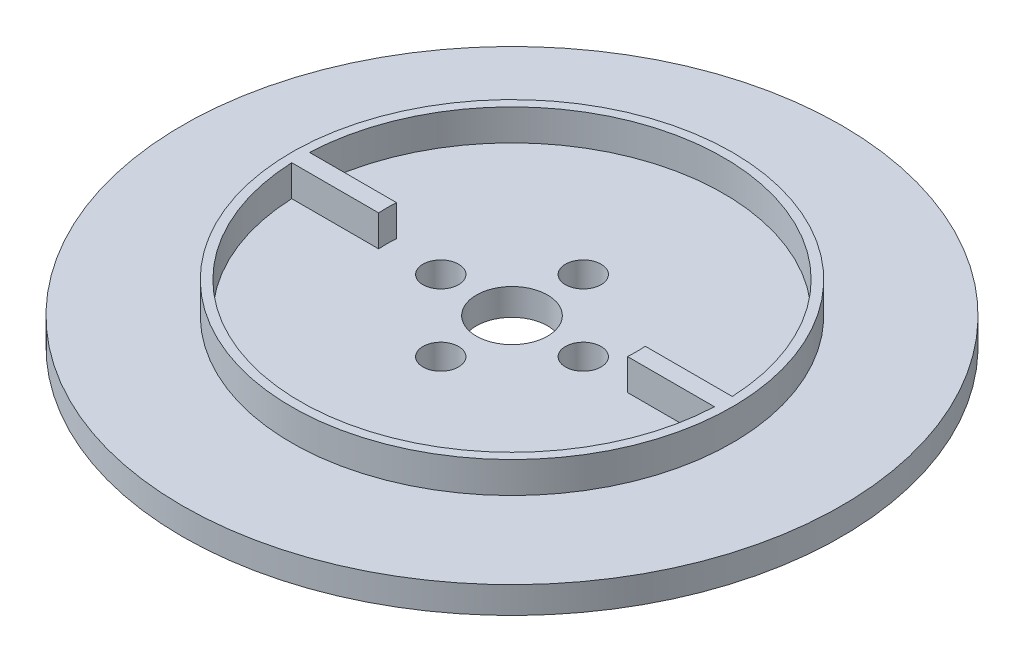
SolidWorks part; units mm, degrees
ref_plane "Front Plane" through (0, 0, 0) normal (0, 0, 1) x (1, 0, 0)
ref_plane "Top Plane" through (0, 0, 0) normal (0, 1, 0) x (1, 0, 0)
ref_plane "Right Plane" through (0, 0, 0) normal (1, 0, 0) x (0, 0, -1)
sketch "Sketch1" plane through (0, 0, 0) normal (0, 1, 0) x (1, 0, 0)
  line L1 (-35, -1) -> (35, -1)
  line L2 (-35, -1) -> (-35, 1)
  line L3 (-35, 1) -> (35, 1)
  line L4 (35, -1) -> (35, 1)
  line L5 (-35, -1) -> (35, 1) construction
  line L6 (-35, 1) -> (35, -1) construction
  circle A0 centre (0, 0) radius 37
  circle A1 centre (0, 0) radius 24.75
  circle A2 centre (0, 0) radius 23.75
  circle A3 centre (0, 0) radius 14
  dimension "D1" = 74
  dimension "D2" = 49.5
  dimension "D3" = 47.5
  dimension "D6" = 28
  dimension "D4" = 70
  dimension "D5" = 2
extrude "Boss-Extrude1" add sketch "Sketch1" along normal blind 3 contours A0
extrude "Boss-Extrude2" add sketch "Sketch1<3>" along normal blind 6.5 contours A2 L3 A1 | A2 L1 A1 | A2 L3 A1 L1 | A3 L3 A2 L1 | A3 L1 A2 L3 | A2 L1 A1 L3 region at (-24.2431, 0, 0) region at (-24.2294, 0, 1.5487) region at (-18.8655, 0, 0) region at (0, 0, -24.2013) region at (24.2431, 0, 0) region at (18.8655, 0, 0)
sketch "Sketch1<3>" plane through (0, 0, 0) normal (0, 1, 0) x (1, 0, 0) same geometry as "Sketch1"
sketch "Sketch3" plane through (0, 3, 0) normal (0, 1, 0) x (1, 0, 0)
  circle A0 centre (0, 0) radius 4
  circle A1 centre (8, 0) radius 2
  circle A2 centre (0, -8) radius 2
  circle A3 centre (-8, 0) radius 2
  circle A4 centre (0, 8) radius 2
  point P15 (0, 0)
  dimension "D1" = 8
  dimension "D3" = 4
  dimension "D2" = 8
  dimension "D4" = 4
extrude "Cut-Extrude1" cut sketch "Sketch3" against normal blind 6.5
